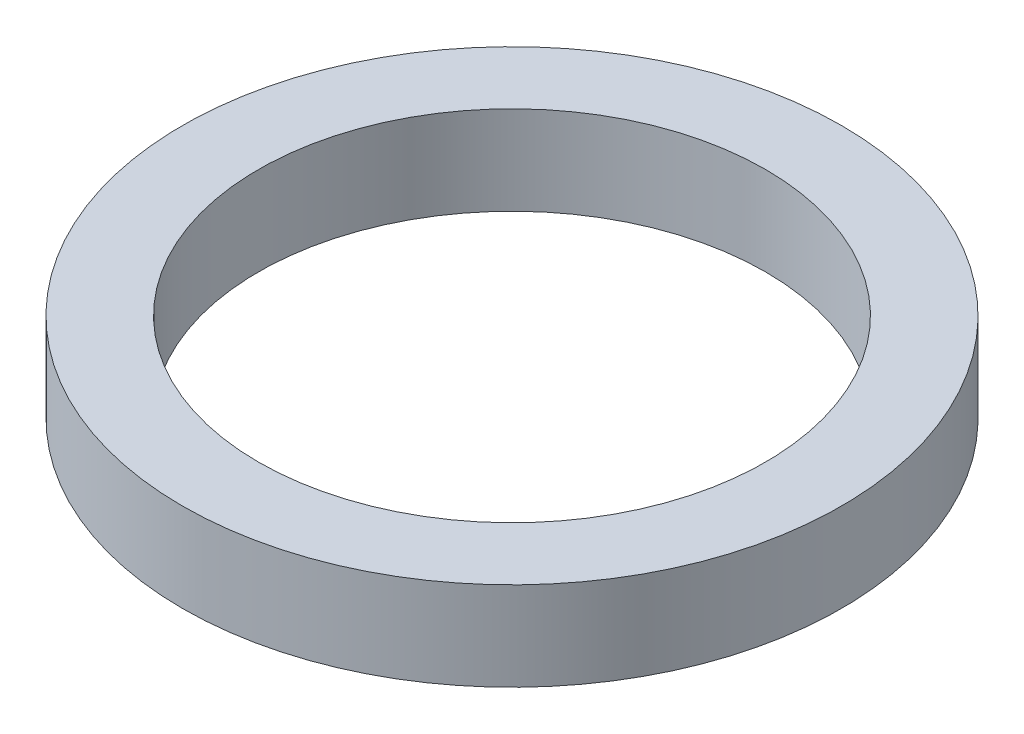
SolidWorks part; units mm, degrees
ref_plane "Front Plane" through (0, 0, 0) normal (0, 0, 1) x (1, 0, 0)
ref_plane "Top Plane" through (0, 0, 0) normal (0, 1, 0) x (1, 0, 0)
ref_plane "Right Plane" through (0, 0, 0) normal (1, 0, 0) x (0, 0, -1)
other "Bounding Box"
ref_plane "Default Plane" through (-8.9266, -12.7485, 0) normal (-0.1736, 0.9848, 0) x (0.9848, 0.1736, 0)
sketch "Sketch2" plane through (0, 0, 0) normal (0, 1, 0) x (1, 0, 0)
  circle A0 centre (0, 0) radius 20
  circle A1 centre (0, 0) radius 26
  dimension "D1" = 40
  dimension "D2" = 52
extrude "Boss-Extrude1" add sketch "Sketch2" along normal mid plane 7
